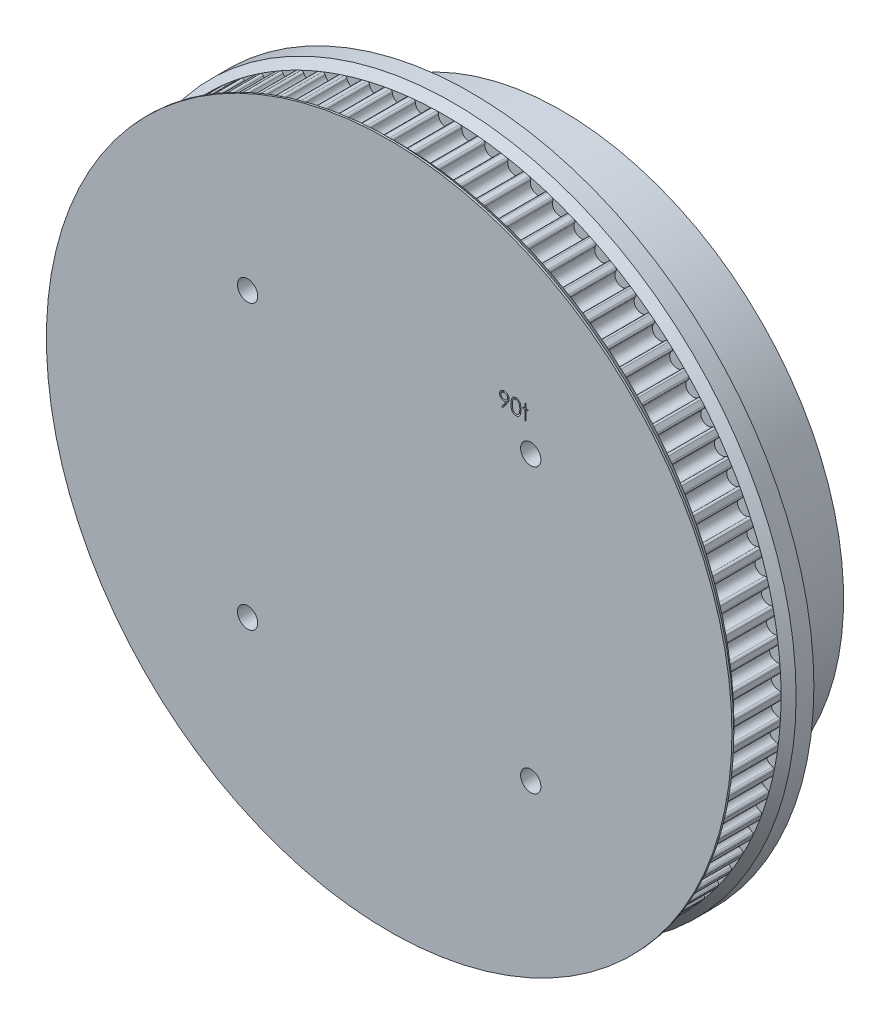
SolidWorks part; units mm, degrees
ref_plane "Front Plane" through (0, 0, 0) normal (0, 0, 1) x (1, 0, 0)
ref_plane "Top Plane" through (0, 0, 0) normal (0, 1, 0) x (1, 0, 0)
ref_plane "Right Plane" through (0, 0, 0) normal (1, 0, 0) x (0, 0, -1)
sketch "Sketch1" plane through (0, 0, 0) normal (0, 0, 1) x (1, 0, 0)
  line L0 (0, 71.6197) -> (0, 0) construction
  line L1 (0, 0) -> (4.9959, 71.4453) construction
  line L2 (0, 70.4947) -> (1.9534, 70.5727) construction
  line L3 (2.9742, 70.537) -> (4.9175, 70.323) construction
  line L4 (1.9534, 70.5727) -> (1.9653, 71.0025) construction
  line L5 (2.9742, 70.537) -> (2.9923, 70.9667) construction
  arc A0 (0, 71.6197) -> (4.9959, 71.4453) centre (0, 0) cw construction
  circle A1 centre (0, 0) radius 71.6197 construction
  circle A2 centre (0, 0) radius 71.0297
  circle A3 centre (0, 0) radius 68.9697
  circle A8 centre (0, 0) radius 72.7697 construction
  circle A9 centre (0, 70.4947) radius 1.525
  circle A10 centre (4.9175, 70.323) radius 1.525
  circle A11 centre (1.9534, 70.5727) radius 0.43
  circle A12 centre (2.9742, 70.537) radius 0.43
  point P18 (0, 68.9697)
  point P19 (4.2572, 15.8881)
  point P20 (4.2572, 15.8881)
  point P21 (1.5238, 70.5555)
  point P23 (3.4016, 70.49)
  dimension "D6" = 3.05
  dimension "D7" = 3.05
  dimension "D8" = 0.86
  dimension "D9" = 0.86
  dimension "D5" = 3.8
  dimension "D2" = 5
  dimension "D3" = 0.59
  dimension "D4" = 2.06
extrude "Boss-Extrude1" add sketch "Sketch1" along normal blind 10 contours A2
extrude "Cut-Extrude1" cut sketch "Sketch1<5>" along normal through all contours A11 A2 A9 | A12 A10 A2 | A9 | A10 region at (3.3605, 70.8449, 0) region at (1.5896, 70.9067, 0)
sketch "Sketch1<5>" plane through (0, 0, 0) normal (0, 0, 1) x (1, 0, 0) same geometry as "Sketch1"
pattern_circular "CirPattern3" count 90 over 360 about axis through (0, 0, 10) along (0, 0, 1) of "Cut-Extrude1"
sketch "Sketch2" plane through (0, 0, 10) normal (0, 0, 1) x (1, 0, 0)
  circle A0 centre (0, 0) radius 72.7697 construction
  arc A81 (-46.5195, 53.0692) -> (-44.1849, 55.0282) centre (-45.3131, 54.0021) ccw
  arc A82 (-46.5195, 53.0692) -> (-44.1849, 55.0282) centre (-45.3131, 54.0021) ccw
  arc A83 (-46.5195, 53.0692) -> (-47.1451, 53.1278) centre (-46.8597, 52.8062) ccw
  arc A84 (-46.5195, 53.0692) -> (-47.1451, 53.1278) centre (-46.8597, 52.8062) ccw
  arc A85 (-47.1451, 53.1278) -> (-47.9088, 52.4402) centre (0, 0) ccw
  arc A86 (-47.1451, 53.1278) -> (-47.9088, 52.4402) centre (0, 0) ccw
  arc A87 (-47.9088, 52.4402) -> (-47.9159, 51.8119) centre (-47.6187, 52.1227) ccw
  arc A88 (-47.9088, 52.4402) -> (-47.9159, 51.8119) centre (-47.6187, 52.1227) ccw
  arc A89 (-50.1081, 49.6949) -> (-47.9159, 51.8119) centre (-48.9698, 50.7097) ccw
  arc A90 (-50.1081, 49.6949) -> (-47.9159, 51.8119) centre (-48.9698, 50.7097) ccw
  arc A91 (-50.1081, 49.6949) -> (-50.7363, 49.7097) centre (-50.4291, 49.4088) ccw
  arc A92 (-50.1081, 49.6949) -> (-50.7363, 49.7097) centre (-50.4291, 49.4088) ccw
  arc A93 (-50.7363, 49.7097) -> (-51.4501, 48.9705) centre (0, 0) ccw
  arc A95 (-50.7363, 49.7097) -> (-51.4501, 48.9705) centre (0, 0) ccw
  arc A97 (-51.4501, 48.9705) -> (-51.4134, 48.3433) centre (-51.1386, 48.674) ccw
  arc A99 (-51.4501, 48.9705) -> (-51.4134, 48.3433) centre (-51.1386, 48.674) ccw
  arc A101 (-53.4526, 46.0785) -> (-51.4134, 48.3433) centre (-52.3878, 47.1702) ccw
  arc A103 (-53.4526, 46.0785) -> (-51.4134, 48.3433) centre (-52.3878, 47.1702) ccw
  arc A105 (-53.4526, 46.0785) -> (-54.0802, 46.0494) centre (-53.7528, 45.7707) ccw
  arc A107 (-53.4526, 46.0785) -> (-54.0802, 46.0494) centre (-53.7528, 45.7707) ccw
  arc A109 (-54.0802, 46.0494) -> (-54.7408, 45.2622) centre (0, 0) ccw
  arc A111 (-54.0802, 46.0494) -> (-54.7408, 45.2622) centre (0, 0) ccw
  arc A112 (-54.7408, 45.2622) -> (-54.6604, 44.6391) centre (-54.4094, 44.9882) ccw
  arc A114 (-54.7408, 45.2622) -> (-54.6604, 44.6391) centre (-54.4094, 44.9882) ccw
  arc A116 (-56.5367, 42.2376) -> (-54.6604, 44.6391) centre (-55.5506, 43.4009) ccw
  arc A118 (-56.5367, 42.2376) -> (-54.6604, 44.6391) centre (-55.5506, 43.4009) ccw
  arc A122 (-56.5367, 42.2376) -> (-57.1607, 42.1648) centre (-56.8147, 41.9096) ccw
  arc A126 (-56.5367, 42.2376) -> (-57.1607, 42.1648) centre (-56.8147, 41.9096) ccw
  arc A130 (-57.1607, 42.1648) -> (-57.7648, 41.3335) centre (0, 0) ccw
  arc A134 (-57.1607, 42.1648) -> (-57.7648, 41.3335) centre (0, 0) ccw
  arc A138 (-57.7648, 41.3335) -> (-57.6411, 40.7174) centre (-57.4151, 41.0832) ccw
  arc A142 (-57.7648, 41.3335) -> (-57.6411, 40.7174) centre (-57.4151, 41.0832) ccw
  arc A146 (-59.3453, 38.1909) -> (-57.6411, 40.7174) centre (-58.4428, 39.4201) ccw
  arc A150 (-59.3453, 38.1909) -> (-57.6411, 40.7174) centre (-58.4428, 39.4201) ccw
  arc A154 (-59.3453, 38.1909) -> (-59.9628, 38.0748) centre (-59.5998, 37.8443) ccw
  arc A158 (-59.3453, 38.1909) -> (-59.9628, 38.0748) centre (-59.5998, 37.8443) ccw
  arc A162 (-59.9628, 38.0748) -> (-60.5073, 37.2033) centre (0, 0) ccw
  arc A166 (-59.9628, 38.0748) -> (-60.5073, 37.2033) centre (0, 0) ccw
  arc A170 (-60.5073, 37.2033) -> (-60.341, 36.5974) centre (-60.141, 36.9781) ccw
  arc A174 (-60.5073, 37.2033) -> (-60.341, 36.5974) centre (-60.141, 36.9781) ccw
  arc A178 (-61.8648, 33.9581) -> (-60.341, 36.5974) centre (-61.0502, 35.2474) ccw
  arc A182 (-61.8648, 33.9581) -> (-60.341, 36.5974) centre (-61.0502, 35.2474) ccw
  arc A186 (-61.8648, 33.9581) -> (-62.4727, 33.7992) centre (-62.0945, 33.5946) ccw
  arc A190 (-61.8648, 33.9581) -> (-62.4727, 33.7992) centre (-62.0945, 33.5946) ccw
  arc A193 (-62.4727, 33.7992) -> (-62.9551, 32.8919) centre (0, 0) ccw
  arc A195 (-62.4727, 33.7992) -> (-62.9551, 32.8919) centre (0, 0) ccw
  arc A197 (-62.9551, 32.8919) -> (-62.7469, 32.2991) centre (-62.574, 32.6928) ccw
  arc A199 (-62.9551, 32.8919) -> (-62.7469, 32.2991) centre (-62.574, 32.6928) ccw
  arc A201 (-64.0829, 29.5599) -> (-62.7469, 32.2991) centre (-63.3602, 30.9029) ccw
  arc A203 (-64.0829, 29.5599) -> (-62.7469, 32.2991) centre (-63.3602, 30.9029) ccw
  arc A205 (-64.0829, 29.5599) -> (-64.6782, 29.359) centre (-64.2867, 29.1813) ccw
  arc A207 (-64.0829, 29.5599) -> (-64.6782, 29.359) centre (-64.2867, 29.1813) ccw
  arc A209 (-64.6782, 29.359) -> (-65.0962, 28.4202) centre (0, 0) ccw
  arc A211 (-64.6782, 29.359) -> (-65.0962, 28.4202) centre (0, 0) ccw
  arc A213 (-65.0962, 28.4202) -> (-64.8471, 27.8434) centre (-64.7021, 28.2482) ccw
  arc A215 (-65.0962, 28.4202) -> (-64.8471, 27.8434) centre (-64.7021, 28.2482) ccw
  arc A217 (-65.9888, 25.0177) -> (-64.8471, 27.8434) centre (-65.3616, 26.4078) ccw
  arc A221 (-65.9888, 25.0177) -> (-64.8471, 27.8434) centre (-65.3616, 26.4078) ccw
  arc A225 (-65.9888, 25.0177) -> (-66.5686, 24.7758) centre (-66.1656, 24.6258) ccw
  arc A229 (-65.9888, 25.0177) -> (-66.5686, 24.7758) centre (-66.1656, 24.6258) ccw
  arc A233 (-66.5686, 24.7758) -> (-66.9201, 23.8101) centre (0, 0) ccw
  arc A241 (-66.5686, 24.7758) -> (-66.9201, 23.8101) centre (0, 0) ccw
  arc A245 (-66.9201, 23.8101) -> (-66.6314, 23.2521) centre (-66.515, 23.666) ccw
  arc A247 (-66.9201, 23.8101) -> (-66.6314, 23.2521) centre (-66.515, 23.666) ccw
  arc A249 (-67.5732, 20.3537) -> (-66.6314, 23.2521) centre (-67.0445, 21.7841) ccw
  arc A251 (-67.5732, 20.3537) -> (-66.6314, 23.2521) centre (-67.0445, 21.7841) ccw
  arc A253 (-67.5732, 20.3537) -> (-68.1347, 20.0718) centre (-67.7223, 19.9503) ccw
  arc A255 (-67.5732, 20.3537) -> (-68.1347, 20.0718) centre (-67.7223, 19.9503) ccw
  arc A257 (-68.1347, 20.0718) -> (-68.418, 19.084) centre (0, 0) ccw
  arc A259 (-68.1347, 20.0718) -> (-68.418, 19.084) centre (0, 0) ccw
  arc A261 (-68.418, 19.084) -> (-68.0911, 18.5475) centre (-68.0038, 18.9685) ccw
  arc A263 (-68.418, 19.084) -> (-68.0911, 18.5475) centre (-68.0038, 18.9685) ccw
  arc A373 (3.4016, 70.49) -> (6.4418, 70.2774) centre (4.9175, 70.323) ccw
  arc A374 (3.4016, 70.49) -> (2.9923, 70.9667) centre (2.9742, 70.537) ccw
  arc A375 (2.9923, 70.9667) -> (1.9653, 71.0025) centre (0, 0) ccw
  arc A376 (1.9653, 71.0025) -> (1.5238, 70.5555) centre (1.9534, 70.5727) ccw
  arc A377 (-1.5238, 70.5555) -> (1.5238, 70.5555) centre (0, 70.4947) ccw
  arc A378 (-1.5238, 70.5555) -> (-1.9653, 71.0025) centre (-1.9534, 70.5727) ccw
  arc A379 (-1.9653, 71.0025) -> (-2.9923, 70.9667) centre (0, 0) ccw
  arc A380 (-2.9923, 70.9667) -> (-3.4016, 70.49) centre (-2.9742, 70.537) ccw
  arc A381 (-6.4418, 70.2774) -> (-3.4016, 70.49) centre (-4.9175, 70.323) ccw
  arc A382 (-6.4418, 70.2774) -> (-6.9134, 70.6925) centre (-6.8716, 70.2645) ccw
  arc A383 (-6.9134, 70.6925) -> (-7.9354, 70.5851) centre (0, 0) ccw
  arc A384 (-7.9354, 70.5851) -> (-8.3105, 70.081) centre (-7.8874, 70.1578) ccw
  arc A385 (-11.3284, 69.6568) -> (-8.3105, 70.081) centre (-9.811, 69.8087) ccw
  arc A386 (-11.3284, 69.6568) -> (-11.8279, 70.038) centre (-11.7563, 69.614) ccw
  arc A387 (-11.8279, 70.038) -> (-12.8399, 69.8596) centre (0, 0) ccw
  arc A388 (-12.8399, 69.8596) -> (-13.1788, 69.3305) centre (-12.7621, 69.4367) ccw
  arc A389 (-16.1598, 68.6969) -> (-13.1788, 69.3305) centre (-14.6567, 68.9542) ccw
  arc A390 (-16.1598, 68.6969) -> (-16.6847, 69.0423) centre (-16.5836, 68.6244) ccw
  arc A391 (-16.6847, 69.0423) -> (-17.6817, 68.7937) centre (0, 0) ccw
  arc A392 (-17.6817, 68.7937) -> (-17.983, 68.2424) centre (-17.5747, 68.3773) ccw
  arc A393 (-20.9125, 67.4023) -> (-17.983, 68.2424) centre (-19.431, 67.7639) ccw
  arc A394 (-20.9125, 67.4023) -> (-21.4602, 67.7103) centre (-21.3302, 67.3004) ccw
  arc A395 (-21.4602, 67.7103) -> (-22.4375, 67.3927) centre (0, 0) ccw
  arc A396 (-22.4375, 67.3927) -> (-22.6995, 66.8217) centre (-22.3016, 66.9848) ccw
  arc A397 (-25.5633, 65.7794) -> (-22.6995, 66.8217) centre (-24.1106, 66.2434) ccw
  arc A398 (-25.5633, 65.7794) -> (-26.1311, 66.0484) centre (-25.9729, 65.6485) ccw
  arc A399 (-26.1311, 66.0484) -> (-27.0839, 65.6634) centre (0, 0) ccw
  arc A400 (-27.0839, 65.6634) -> (-27.3055, 65.0755) centre (-26.9199, 65.2659) ccw
  arc A401 (-30.0896, 63.8359) -> (-27.3055, 65.0755) centre (-28.6728, 64.4001) ccw
  arc A402 (-30.0896, 63.8359) -> (-30.6748, 64.0647) centre (-30.4891, 63.6768) ccw
  arc A403 (-30.6748, 64.0647) -> (-31.5984, 63.6142) centre (0, 0) ccw
  arc A404 (-31.5984, 63.6142) -> (-31.7784, 63.0122) centre (-31.4071, 63.2291) ccw
  arc A405 (-34.4692, 61.5815) -> (-31.7784, 63.0122) centre (-33.0953, 62.2431) ccw
  arc A406 (-34.4692, 61.5815) -> (-35.069, 61.7688) centre (-34.8567, 61.3949) ccw
  arc A407 (-35.069, 61.7688) -> (-35.9589, 61.255) centre (0, 0) ccw
  arc A408 (-35.9589, 61.255) -> (-36.0965, 60.642) centre (-35.7412, 60.8842) ccw
  arc A409 (-38.681, 59.027) -> (-36.0965, 60.642) centre (-37.3565, 59.7829) ccw
  arc A410 (-38.681, 59.027) -> (-39.2923, 59.1721) centre (-39.0544, 58.8139) ccw
  arc A411 (-39.2923, 59.1721) -> (-40.1442, 58.5975) centre (0, 0) ccw
  arc A412 (-40.1442, 58.5975) -> (-40.2387, 57.9763) centre (-39.9012, 58.2427) ccw
  arc A413 (-42.7043, 56.185) -> (-40.2387, 57.9763) centre (-41.4358, 57.0314) ccw
  arc A414 (-42.7043, 56.185) -> (-43.3242, 56.2871) centre (-43.062, 55.9463) ccw
  arc A415 (-43.3242, 56.2871) -> (-44.134, 55.6544) centre (0, 0) ccw
  arc A416 (-44.134, 55.6544) -> (-44.1849, 55.0282) centre (-43.8668, 55.3175) ccw
  arc A649 (3.4016, 70.49) -> (6.4418, 70.2774) centre (4.9175, 70.323) ccw
  arc A650 (3.4016, 70.49) -> (2.9923, 70.9667) centre (2.9742, 70.537) ccw
  arc A651 (2.9923, 70.9667) -> (1.9653, 71.0025) centre (0, 0) ccw
  arc A652 (1.9653, 71.0025) -> (1.5238, 70.5555) centre (1.9534, 70.5727) ccw
  arc A653 (-1.5238, 70.5555) -> (1.5238, 70.5555) centre (0, 70.4947) ccw
  arc A654 (-1.5238, 70.5555) -> (-1.9653, 71.0025) centre (-1.9534, 70.5727) ccw
  arc A655 (-1.9653, 71.0025) -> (-2.9923, 70.9667) centre (0, 0) ccw
  arc A656 (-2.9923, 70.9667) -> (-3.4016, 70.49) centre (-2.9742, 70.537) ccw
  arc A657 (-6.4418, 70.2774) -> (-3.4016, 70.49) centre (-4.9175, 70.323) ccw
  arc A658 (-6.4418, 70.2774) -> (-6.9134, 70.6925) centre (-6.8716, 70.2645) ccw
  arc A659 (-6.9134, 70.6925) -> (-7.9354, 70.5851) centre (0, 0) ccw
  arc A660 (-7.9354, 70.5851) -> (-8.3105, 70.081) centre (-7.8874, 70.1578) ccw
  arc A661 (-11.3284, 69.6568) -> (-8.3105, 70.081) centre (-9.811, 69.8087) ccw
  arc A662 (-11.3284, 69.6568) -> (-11.8279, 70.038) centre (-11.7563, 69.614) ccw
  arc A663 (-11.8279, 70.038) -> (-12.8399, 69.8596) centre (0, 0) ccw
  arc A664 (-12.8399, 69.8596) -> (-13.1788, 69.3305) centre (-12.7621, 69.4367) ccw
  arc A665 (-16.1598, 68.6969) -> (-13.1788, 69.3305) centre (-14.6567, 68.9542) ccw
  arc A666 (-16.1598, 68.6969) -> (-16.6847, 69.0423) centre (-16.5836, 68.6244) ccw
  arc A667 (-16.6847, 69.0423) -> (-17.6817, 68.7937) centre (0, 0) ccw
  arc A668 (-17.6817, 68.7937) -> (-17.983, 68.2424) centre (-17.5747, 68.3773) ccw
  arc A669 (-20.9125, 67.4023) -> (-17.983, 68.2424) centre (-19.431, 67.7639) ccw
  arc A670 (-20.9125, 67.4023) -> (-21.4602, 67.7103) centre (-21.3302, 67.3004) ccw
  arc A671 (-21.4602, 67.7103) -> (-22.4375, 67.3927) centre (0, 0) ccw
  arc A672 (-22.4375, 67.3927) -> (-22.6995, 66.8217) centre (-22.3016, 66.9848) ccw
  arc A673 (-25.5633, 65.7794) -> (-22.6995, 66.8217) centre (-24.1106, 66.2434) ccw
  arc A674 (-25.5633, 65.7794) -> (-26.1311, 66.0484) centre (-25.9729, 65.6485) ccw
  arc A675 (-26.1311, 66.0484) -> (-27.0839, 65.6634) centre (0, 0) ccw
  arc A676 (-27.0839, 65.6634) -> (-27.3055, 65.0755) centre (-26.9199, 65.2659) ccw
  arc A677 (-30.0896, 63.8359) -> (-27.3055, 65.0755) centre (-28.6728, 64.4001) ccw
  arc A678 (-30.0896, 63.8359) -> (-30.6748, 64.0647) centre (-30.4891, 63.6768) ccw
  arc A679 (-30.6748, 64.0647) -> (-31.5984, 63.6142) centre (0, 0) ccw
  arc A680 (-31.5984, 63.6142) -> (-31.7784, 63.0122) centre (-31.4071, 63.2291) ccw
  arc A681 (-34.4692, 61.5815) -> (-31.7784, 63.0122) centre (-33.0953, 62.2431) ccw
  arc A682 (-34.4692, 61.5815) -> (-35.069, 61.7688) centre (-34.8567, 61.3949) ccw
  arc A683 (-35.069, 61.7688) -> (-35.9589, 61.255) centre (0, 0) ccw
  arc A684 (-35.9589, 61.255) -> (-36.0965, 60.642) centre (-35.7412, 60.8842) ccw
  arc A685 (-38.681, 59.027) -> (-36.0965, 60.642) centre (-37.3565, 59.7829) ccw
  arc A686 (-38.681, 59.027) -> (-39.2923, 59.1721) centre (-39.0544, 58.8139) ccw
  arc A687 (-39.2923, 59.1721) -> (-40.1442, 58.5975) centre (0, 0) ccw
  arc A688 (-40.1442, 58.5975) -> (-40.2387, 57.9763) centre (-39.9012, 58.2427) ccw
  arc A689 (-42.7043, 56.185) -> (-40.2387, 57.9763) centre (-41.4358, 57.0314) ccw
  arc A690 (-42.7043, 56.185) -> (-43.3242, 56.2871) centre (-43.062, 55.9463) ccw
  arc A691 (-43.3242, 56.2871) -> (-44.134, 55.6544) centre (0, 0) ccw
  arc A692 (-44.134, 55.6544) -> (-44.1849, 55.0282) centre (-43.8668, 55.3175) ccw
  arc A1359 (-6.9134, -70.6925) -> (-6.4418, -70.2774) centre (-6.8716, -70.2645) ccw
  arc A1361 (-6.9134, -70.6925) -> (-6.4418, -70.2774) centre (-6.8716, -70.2645) ccw
  arc A1363 (-3.4016, -70.49) -> (-6.4418, -70.2774) centre (-4.9175, -70.323) ccw
  arc A1365 (-3.4016, -70.49) -> (-6.4418, -70.2774) centre (-4.9175, -70.323) ccw
  arc A1367 (-3.4016, -70.49) -> (-2.9923, -70.9667) centre (-2.9742, -70.537) ccw
  arc A1369 (-3.4016, -70.49) -> (-2.9923, -70.9667) centre (-2.9742, -70.537) ccw
  arc A1371 (-2.9923, -70.9667) -> (-1.9653, -71.0025) centre (0, 0) ccw
  arc A1373 (-2.9923, -70.9667) -> (-1.9653, -71.0025) centre (0, 0) ccw
  arc A1375 (-1.9653, -71.0025) -> (-1.5238, -70.5555) centre (-1.9534, -70.5727) ccw
  arc A1377 (-1.9653, -71.0025) -> (-1.5238, -70.5555) centre (-1.9534, -70.5727) ccw
  arc A1379 (1.5238, -70.5555) -> (-1.5238, -70.5555) centre (0, -70.4947) ccw
  arc A1381 (1.5238, -70.5555) -> (-1.5238, -70.5555) centre (0, -70.4947) ccw
  arc A1383 (1.5238, -70.5555) -> (1.9653, -71.0025) centre (1.9534, -70.5727) ccw
  arc A1385 (1.5238, -70.5555) -> (1.9653, -71.0025) centre (1.9534, -70.5727) ccw
  arc A1387 (1.9653, -71.0025) -> (2.9923, -70.9667) centre (0, 0) ccw
  arc A1389 (1.9653, -71.0025) -> (2.9923, -70.9667) centre (0, 0) ccw
  arc A1391 (2.9923, -70.9667) -> (3.4016, -70.49) centre (2.9742, -70.537) ccw
  arc A1393 (2.9923, -70.9667) -> (3.4016, -70.49) centre (2.9742, -70.537) ccw
  arc A1395 (6.4418, -70.2774) -> (3.4016, -70.49) centre (4.9175, -70.323) ccw
  arc A1397 (6.4418, -70.2774) -> (3.4016, -70.49) centre (4.9175, -70.323) ccw
  arc A1399 (6.4418, -70.2774) -> (6.9134, -70.6925) centre (6.8716, -70.2645) ccw
  arc A1401 (6.4418, -70.2774) -> (6.9134, -70.6925) centre (6.8716, -70.2645) ccw
  arc A1403 (6.9134, -70.6925) -> (7.9354, -70.5851) centre (0, 0) ccw
  arc A1405 (6.9134, -70.6925) -> (7.9354, -70.5851) centre (0, 0) ccw
  arc A1407 (7.9354, -70.5851) -> (8.3105, -70.081) centre (7.8874, -70.1578) ccw
  arc A1409 (7.9354, -70.5851) -> (8.3105, -70.081) centre (7.8874, -70.1578) ccw
  arc A1411 (11.3284, -69.6568) -> (8.3105, -70.081) centre (9.811, -69.8087) ccw
  arc A1413 (11.3284, -69.6568) -> (8.3105, -70.081) centre (9.811, -69.8087) ccw
  arc A1415 (11.3284, -69.6568) -> (11.8279, -70.038) centre (11.7563, -69.614) ccw
  arc A1417 (11.3284, -69.6568) -> (11.8279, -70.038) centre (11.7563, -69.614) ccw
  arc A1419 (11.8279, -70.038) -> (12.8399, -69.8596) centre (0, 0) ccw
  arc A1421 (11.8279, -70.038) -> (12.8399, -69.8596) centre (0, 0) ccw
  arc A1423 (12.8399, -69.8596) -> (13.1788, -69.3305) centre (12.7621, -69.4367) ccw
  arc A1425 (12.8399, -69.8596) -> (13.1788, -69.3305) centre (12.7621, -69.4367) ccw
  arc A1427 (16.1598, -68.6969) -> (13.1788, -69.3305) centre (14.6567, -68.9542) ccw
  arc A1429 (16.1598, -68.6969) -> (13.1788, -69.3305) centre (14.6567, -68.9542) ccw
  arc A1431 (16.1598, -68.6969) -> (16.6847, -69.0423) centre (16.5836, -68.6244) ccw
  arc A1433 (16.1598, -68.6969) -> (16.6847, -69.0423) centre (16.5836, -68.6244) ccw
  arc A1435 (16.6847, -69.0423) -> (17.6817, -68.7937) centre (0, 0) ccw
  arc A1437 (16.6847, -69.0423) -> (17.6817, -68.7937) centre (0, 0) ccw
  arc A1439 (17.6817, -68.7937) -> (17.983, -68.2424) centre (17.5747, -68.3773) ccw
  arc A1441 (17.6817, -68.7937) -> (17.983, -68.2424) centre (17.5747, -68.3773) ccw
  arc A1443 (20.9125, -67.4023) -> (17.983, -68.2424) centre (19.431, -67.7639) ccw
  arc A1445 (20.9125, -67.4023) -> (17.983, -68.2424) centre (19.431, -67.7639) ccw
  arc A1447 (20.9125, -67.4023) -> (21.4602, -67.7103) centre (21.3302, -67.3004) ccw
  arc A1449 (20.9125, -67.4023) -> (21.4602, -67.7103) centre (21.3302, -67.3004) ccw
  arc A1451 (21.4602, -67.7103) -> (22.4375, -67.3927) centre (0, 0) ccw
  arc A1453 (21.4602, -67.7103) -> (22.4375, -67.3927) centre (0, 0) ccw
  arc A1455 (22.4375, -67.3927) -> (22.6995, -66.8217) centre (22.3016, -66.9848) ccw
  arc A1457 (22.4375, -67.3927) -> (22.6995, -66.8217) centre (22.3016, -66.9848) ccw
  arc A1459 (25.5633, -65.7794) -> (22.6995, -66.8217) centre (24.1106, -66.2434) ccw
  arc A1461 (25.5633, -65.7794) -> (22.6995, -66.8217) centre (24.1106, -66.2434) ccw
  arc A1463 (25.5633, -65.7794) -> (26.1311, -66.0484) centre (25.9729, -65.6485) ccw
  arc A1465 (25.5633, -65.7794) -> (26.1311, -66.0484) centre (25.9729, -65.6485) ccw
  arc A1467 (26.1311, -66.0484) -> (27.0839, -65.6634) centre (0, 0) ccw
  arc A1469 (26.1311, -66.0484) -> (27.0839, -65.6634) centre (0, 0) ccw
  arc A1471 (27.0839, -65.6634) -> (27.3055, -65.0755) centre (26.9199, -65.2659) ccw
  arc A1473 (27.0839, -65.6634) -> (27.3055, -65.0755) centre (26.9199, -65.2659) ccw
  arc A1475 (30.0896, -63.8359) -> (27.3055, -65.0755) centre (28.6728, -64.4001) ccw
  arc A1477 (30.0896, -63.8359) -> (27.3055, -65.0755) centre (28.6728, -64.4001) ccw
  arc A1479 (30.0896, -63.8359) -> (30.6748, -64.0647) centre (30.4891, -63.6768) ccw
  arc A1481 (30.0896, -63.8359) -> (30.6748, -64.0647) centre (30.4891, -63.6768) ccw
  arc A1483 (30.6748, -64.0647) -> (31.5984, -63.6142) centre (0, 0) ccw
  arc A1485 (30.6748, -64.0647) -> (31.5984, -63.6142) centre (0, 0) ccw
  arc A1487 (31.5984, -63.6142) -> (31.7784, -63.0122) centre (31.4071, -63.2291) ccw
  arc A1489 (31.5984, -63.6142) -> (31.7784, -63.0122) centre (31.4071, -63.2291) ccw
  arc A1491 (34.4692, -61.5815) -> (31.7784, -63.0122) centre (33.0953, -62.2431) ccw
  arc A1493 (34.4692, -61.5815) -> (31.7784, -63.0122) centre (33.0953, -62.2431) ccw
  arc A1495 (34.4692, -61.5815) -> (35.069, -61.7688) centre (34.8567, -61.3949) ccw
  arc A1497 (34.4692, -61.5815) -> (35.069, -61.7688) centre (34.8567, -61.3949) ccw
  arc A1499 (35.069, -61.7688) -> (35.9589, -61.255) centre (0, 0) ccw
  arc A1501 (35.069, -61.7688) -> (35.9589, -61.255) centre (0, 0) ccw
  arc A1503 (35.9589, -61.255) -> (36.0965, -60.642) centre (35.7412, -60.8842) ccw
  arc A1505 (35.9589, -61.255) -> (36.0965, -60.642) centre (35.7412, -60.8842) ccw
  arc A1507 (38.681, -59.027) -> (36.0965, -60.642) centre (37.3565, -59.7829) ccw
  arc A1509 (38.681, -59.027) -> (36.0965, -60.642) centre (37.3565, -59.7829) ccw
  arc A1511 (38.681, -59.027) -> (39.2923, -59.1721) centre (39.0544, -58.8139) ccw
  arc A1513 (38.681, -59.027) -> (39.2923, -59.1721) centre (39.0544, -58.8139) ccw
  arc A1515 (39.2923, -59.1721) -> (40.1442, -58.5975) centre (0, 0) ccw
  arc A1517 (39.2923, -59.1721) -> (40.1442, -58.5975) centre (0, 0) ccw
  arc A1519 (40.1442, -58.5975) -> (40.2387, -57.9763) centre (39.9012, -58.2427) ccw
  arc A1521 (40.1442, -58.5975) -> (40.2387, -57.9763) centre (39.9012, -58.2427) ccw
  arc A1523 (42.7043, -56.185) -> (40.2387, -57.9763) centre (41.4358, -57.0314) ccw
  arc A1525 (42.7043, -56.185) -> (40.2387, -57.9763) centre (41.4358, -57.0314) ccw
  arc A1527 (42.7043, -56.185) -> (43.3242, -56.2871) centre (43.062, -55.9463) ccw
  arc A1529 (42.7043, -56.185) -> (43.3242, -56.2871) centre (43.062, -55.9463) ccw
  arc A1531 (43.3242, -56.2871) -> (44.134, -55.6544) centre (0, 0) ccw
  arc A1533 (43.3242, -56.2871) -> (44.134, -55.6544) centre (0, 0) ccw
  arc A1535 (44.134, -55.6544) -> (44.1849, -55.0282) centre (43.8668, -55.3175) ccw
  arc A1537 (44.134, -55.6544) -> (44.1849, -55.0282) centre (43.8668, -55.3175) ccw
  arc A1539 (46.5195, -53.0692) -> (44.1849, -55.0282) centre (45.3131, -54.0021) ccw
  arc A1541 (46.5195, -53.0692) -> (44.1849, -55.0282) centre (45.3131, -54.0021) ccw
  arc A1543 (46.5195, -53.0692) -> (47.1451, -53.1278) centre (46.8597, -52.8062) ccw
  arc A1545 (46.5195, -53.0692) -> (47.1451, -53.1278) centre (46.8597, -52.8062) ccw
  arc A1547 (47.1451, -53.1278) -> (47.9088, -52.4402) centre (0, 0) ccw
  arc A1549 (47.1451, -53.1278) -> (47.9088, -52.4402) centre (0, 0) ccw
  arc A1551 (47.9088, -52.4402) -> (47.9159, -51.8119) centre (47.6187, -52.1227) ccw
  arc A1553 (47.9088, -52.4402) -> (47.9159, -51.8119) centre (47.6187, -52.1227) ccw
  arc A1555 (50.1081, -49.6949) -> (47.9159, -51.8119) centre (48.9698, -50.7097) ccw
  arc A1557 (50.1081, -49.6949) -> (47.9159, -51.8119) centre (48.9698, -50.7097) ccw
  arc A1559 (50.1081, -49.6949) -> (50.7363, -49.7097) centre (50.4291, -49.4088) ccw
  arc A1561 (50.1081, -49.6949) -> (50.7363, -49.7097) centre (50.4291, -49.4088) ccw
  arc A1563 (50.7363, -49.7097) -> (51.4501, -48.9705) centre (0, 0) ccw
  arc A1565 (50.7363, -49.7097) -> (51.4501, -48.9705) centre (0, 0) ccw
  arc A1567 (51.4501, -48.9705) -> (51.4134, -48.3433) centre (51.1386, -48.674) ccw
  arc A1569 (51.4501, -48.9705) -> (51.4134, -48.3433) centre (51.1386, -48.674) ccw
  arc A1571 (53.4526, -46.0785) -> (51.4134, -48.3433) centre (52.3878, -47.1702) ccw
  arc A1573 (53.4526, -46.0785) -> (51.4134, -48.3433) centre (52.3878, -47.1702) ccw
  arc A1575 (53.4526, -46.0785) -> (54.0802, -46.0494) centre (53.7528, -45.7707) ccw
  arc A1577 (53.4526, -46.0785) -> (54.0802, -46.0494) centre (53.7528, -45.7707) ccw
  arc A1579 (54.0802, -46.0494) -> (54.7408, -45.2622) centre (0, 0) ccw
  arc A1581 (54.0802, -46.0494) -> (54.7408, -45.2622) centre (0, 0) ccw
  arc A1583 (54.7408, -45.2622) -> (54.6604, -44.6391) centre (54.4094, -44.9882) ccw
  arc A1585 (54.7408, -45.2622) -> (54.6604, -44.6391) centre (54.4094, -44.9882) ccw
  arc A1587 (56.5367, -42.2376) -> (54.6604, -44.6391) centre (55.5506, -43.4009) ccw
  arc A1589 (56.5367, -42.2376) -> (54.6604, -44.6391) centre (55.5506, -43.4009) ccw
  arc A1591 (56.5367, -42.2376) -> (57.1607, -42.1648) centre (56.8147, -41.9096) ccw
  arc A1593 (56.5367, -42.2376) -> (57.1607, -42.1648) centre (56.8147, -41.9096) ccw
  arc A1595 (57.1607, -42.1648) -> (57.7648, -41.3335) centre (0, 0) ccw
  arc A1596 (57.1607, -42.1648) -> (57.7648, -41.3335) centre (0, 0) ccw
  arc A1597 (57.7648, -41.3335) -> (57.6411, -40.7174) centre (57.4151, -41.0832) ccw
  arc A1598 (57.7648, -41.3335) -> (57.6411, -40.7174) centre (57.4151, -41.0832) ccw
  arc A1599 (59.3453, -38.1909) -> (57.6411, -40.7174) centre (58.4428, -39.4201) ccw
  arc A1600 (59.3453, -38.1909) -> (57.6411, -40.7174) centre (58.4428, -39.4201) ccw
  arc A1601 (59.3453, -38.1909) -> (59.9628, -38.0748) centre (59.5998, -37.8443) ccw
  arc A1602 (59.3453, -38.1909) -> (59.9628, -38.0748) centre (59.5998, -37.8443) ccw
  arc A1603 (59.9628, -38.0748) -> (60.5073, -37.2033) centre (0, 0) ccw
  arc A1604 (59.9628, -38.0748) -> (60.5073, -37.2033) centre (0, 0) ccw
  arc A1605 (60.5073, -37.2033) -> (60.341, -36.5974) centre (60.141, -36.9781) ccw
  arc A1606 (60.5073, -37.2033) -> (60.341, -36.5974) centre (60.141, -36.9781) ccw
  arc A1607 (61.8648, -33.9581) -> (60.341, -36.5974) centre (61.0502, -35.2474) ccw
  arc A1608 (61.8648, -33.9581) -> (60.341, -36.5974) centre (61.0502, -35.2474) ccw
  arc A1609 (61.8648, -33.9581) -> (62.4727, -33.7992) centre (62.0945, -33.5946) ccw
  arc A1610 (61.8648, -33.9581) -> (62.4727, -33.7992) centre (62.0945, -33.5946) ccw
  arc A1611 (62.4727, -33.7992) -> (62.9551, -32.8919) centre (0, 0) ccw
  arc A1612 (62.4727, -33.7992) -> (62.9551, -32.8919) centre (0, 0) ccw
  arc A1613 (62.9551, -32.8919) -> (62.7469, -32.2991) centre (62.574, -32.6928) ccw
  arc A1614 (62.9551, -32.8919) -> (62.7469, -32.2991) centre (62.574, -32.6928) ccw
  arc A1615 (64.0829, -29.5599) -> (62.7469, -32.2991) centre (63.3602, -30.9029) ccw
  arc A1616 (64.0829, -29.5599) -> (62.7469, -32.2991) centre (63.3602, -30.9029) ccw
  arc A1617 (64.0829, -29.5599) -> (64.6782, -29.359) centre (64.2867, -29.1813) ccw
  arc A1618 (64.0829, -29.5599) -> (64.6782, -29.359) centre (64.2867, -29.1813) ccw
  arc A1619 (64.6782, -29.359) -> (65.0962, -28.4202) centre (0, 0) ccw
  arc A1620 (64.6782, -29.359) -> (65.0962, -28.4202) centre (0, 0) ccw
  arc A1621 (65.0962, -28.4202) -> (64.8471, -27.8434) centre (64.7021, -28.2482) ccw
  arc A1622 (65.0962, -28.4202) -> (64.8471, -27.8434) centre (64.7021, -28.2482) ccw
  arc A1623 (65.9888, -25.0177) -> (64.8471, -27.8434) centre (65.3616, -26.4078) ccw
  arc A1624 (65.9888, -25.0177) -> (64.8471, -27.8434) centre (65.3616, -26.4078) ccw
  arc A1625 (65.9888, -25.0177) -> (66.5686, -24.7758) centre (66.1656, -24.6258) ccw
  arc A1626 (65.9888, -25.0177) -> (66.5686, -24.7758) centre (66.1656, -24.6258) ccw
  arc A1627 (66.5686, -24.7758) -> (66.9201, -23.8101) centre (0, 0) ccw
  arc A1628 (66.5686, -24.7758) -> (66.9201, -23.8101) centre (0, 0) ccw
  arc A1629 (66.9201, -23.8101) -> (66.6314, -23.2521) centre (66.515, -23.666) ccw
  arc A1630 (66.9201, -23.8101) -> (66.6314, -23.2521) centre (66.515, -23.666) ccw
  arc A1631 (67.5732, -20.3537) -> (66.6314, -23.2521) centre (67.0445, -21.7841) ccw
  arc A1632 (67.5732, -20.3537) -> (66.6314, -23.2521) centre (67.0445, -21.7841) ccw
  arc A1633 (67.5732, -20.3537) -> (68.1347, -20.0718) centre (67.7223, -19.9503) ccw
  arc A1634 (67.5732, -20.3537) -> (68.1347, -20.0718) centre (67.7223, -19.9503) ccw
  arc A1635 (68.1347, -20.0718) -> (68.418, -19.084) centre (0, 0) ccw
  arc A1636 (68.1347, -20.0718) -> (68.418, -19.084) centre (0, 0) ccw
  arc A1637 (68.418, -19.084) -> (68.0911, -18.5475) centre (68.0038, -18.9685) ccw
  arc A1638 (68.418, -19.084) -> (68.0911, -18.5475) centre (68.0038, -18.9685) ccw
  arc A1639 (68.8284, -15.5904) -> (68.0911, -18.5475) centre (68.4007, -17.0542) ccw
  arc A1640 (68.8284, -15.5904) -> (68.0911, -18.5475) centre (68.4007, -17.0542) ccw
  arc A1641 (68.8284, -15.5904) -> (69.3689, -15.2701) centre (68.949, -15.1777) ccw
  arc A1642 (68.8284, -15.5904) -> (69.3689, -15.2701) centre (68.949, -15.1777) ccw
  arc A1643 (69.3689, -15.2701) -> (69.5826, -14.2649) centre (0, 0) ccw
  arc A1644 (69.3689, -15.2701) -> (69.5826, -14.2649) centre (0, 0) ccw
  arc A1645 (69.5826, -14.2649) -> (69.219, -13.7525) centre (69.1613, -14.1786) ccw
  arc A1646 (69.5826, -14.2649) -> (69.219, -13.7525) centre (69.1613, -14.1786) ccw
  arc A1647 (69.7483, -10.7512) -> (69.219, -13.7525) centre (69.4238, -12.2413) ccw
  arc A1648 (69.7483, -10.7512) -> (69.219, -13.7525) centre (69.4238, -12.2413) ccw
  arc A1649 (69.7483, -10.7512) -> (70.2651, -10.394) centre (69.8397, -10.3311) ccw
  arc A1650 (69.7483, -10.7512) -> (70.2651, -10.394) centre (69.8397, -10.3311) ccw
  arc A1651 (70.2651, -10.394) -> (70.4081, -9.3764) centre (0, 0) ccw
  arc A1652 (70.2651, -10.394) -> (70.4081, -9.3764) centre (0, 0) ccw
  arc A1653 (70.4081, -9.3764) -> (70.0098, -8.8905) centre (69.9819, -9.3196) ccw
  arc A1654 (70.4081, -9.3764) -> (70.0098, -8.8905) centre (69.9819, -9.3196) ccw
  arc A1655 (70.3283, -5.8596) -> (70.0098, -8.8905) centre (70.1085, -7.3687) ccw
  arc A1656 (70.3283, -5.8596) -> (70.0098, -8.8905) centre (70.1085, -7.3687) ccw
  arc A1657 (70.3283, -5.8596) -> (70.819, -5.4672) centre (70.3903, -5.4341) ccw
  arc A1658 (70.3283, -5.8596) -> (70.819, -5.4672) centre (70.3903, -5.4341) ccw
  arc A1659 (70.819, -5.4672) -> (70.8907, -4.4421) centre (0, 0) ccw
  arc A1660 (70.819, -5.4672) -> (70.8907, -4.4421) centre (0, 0) ccw
  arc A1661 (70.8907, -4.4421) -> (70.4594, -3.9852) centre (70.4615, -4.4152) ccw
  arc A1662 (70.8907, -4.4421) -> (70.4594, -3.9852) centre (70.4615, -4.4152) ccw
  arc A1663 (70.5657, -0.9395) -> (70.4594, -3.9852) centre (70.4518, -2.4602) ccw
  arc A1664 (70.5657, -0.9395) -> (70.4594, -3.9852) centre (70.4518, -2.4602) ccw
  arc A1665 (70.5657, -0.9395) -> (71.0279, -0.5138) centre (70.5979, -0.5107) ccw
  arc A1666 (70.5657, -0.9395) -> (71.0279, -0.5138) centre (70.5979, -0.5107) ccw
  arc A1667 (71.0279, -0.5138) -> (71.0279, 0.5138) centre (0, 0) ccw
  arc A1668 (71.0279, -0.5138) -> (71.0279, 0.5138) centre (0, 0) ccw
  arc A1669 (71.0279, 0.5138) -> (70.5657, 0.9395) centre (70.5979, 0.5107) ccw
  arc A1670 (71.0279, 0.5138) -> (70.5657, 0.9395) centre (70.5979, 0.5107) ccw
  arc A1671 (-68.8284, 15.5904) -> (-68.0911, 18.5475) centre (-68.4007, 17.0542) ccw
  arc A1672 (-68.8284, 15.5904) -> (-68.0911, 18.5475) centre (-68.4007, 17.0542) ccw
  arc A1673 (-68.8284, 15.5904) -> (-69.3689, 15.2701) centre (-68.949, 15.1777) ccw
  arc A1674 (-68.8284, 15.5904) -> (-69.3689, 15.2701) centre (-68.949, 15.1777) ccw
  arc A1675 (-69.3689, 15.2701) -> (-69.5826, 14.2649) centre (0, 0) ccw
  arc A1676 (-69.3689, 15.2701) -> (-69.5826, 14.2649) centre (0, 0) ccw
  arc A1677 (-69.5826, 14.2649) -> (-69.219, 13.7525) centre (-69.1613, 14.1786) ccw
  arc A1678 (-69.5826, 14.2649) -> (-69.219, 13.7525) centre (-69.1613, 14.1786) ccw
  arc A1679 (-69.7483, 10.7512) -> (-69.219, 13.7525) centre (-69.4238, 12.2413) ccw
  arc A1680 (-69.7483, 10.7512) -> (-69.219, 13.7525) centre (-69.4238, 12.2413) ccw
  arc A1681 (-69.7483, 10.7512) -> (-70.2651, 10.394) centre (-69.8397, 10.3311) ccw
  arc A1682 (-69.7483, 10.7512) -> (-70.2651, 10.394) centre (-69.8397, 10.3311) ccw
  arc A1683 (-70.2651, 10.394) -> (-70.4081, 9.3764) centre (0, 0) ccw
  arc A1684 (-70.2651, 10.394) -> (-70.4081, 9.3764) centre (0, 0) ccw
  arc A1685 (-70.4081, 9.3764) -> (-70.0098, 8.8905) centre (-69.9819, 9.3196) ccw
  arc A1686 (-70.4081, 9.3764) -> (-70.0098, 8.8905) centre (-69.9819, 9.3196) ccw
  arc A1687 (-70.3283, 5.8596) -> (-70.0098, 8.8905) centre (-70.1085, 7.3687) ccw
  arc A1688 (-70.3283, 5.8596) -> (-70.0098, 8.8905) centre (-70.1085, 7.3687) ccw
  arc A1689 (-70.3283, 5.8596) -> (-70.819, 5.4672) centre (-70.3903, 5.4341) ccw
  arc A1690 (-70.3283, 5.8596) -> (-70.819, 5.4672) centre (-70.3903, 5.4341) ccw
  arc A1691 (-70.819, 5.4672) -> (-70.8907, 4.4421) centre (0, 0) ccw
  arc A1692 (-70.819, 5.4672) -> (-70.8907, 4.4421) centre (0, 0) ccw
  arc A1693 (-70.8907, 4.4421) -> (-70.4594, 3.9852) centre (-70.4615, 4.4152) ccw
  arc A1694 (-70.8907, 4.4421) -> (-70.4594, 3.9852) centre (-70.4615, 4.4152) ccw
  arc A1695 (-70.5657, 0.9395) -> (-70.4594, 3.9852) centre (-70.4518, 2.4602) ccw
  arc A1696 (-70.5657, 0.9395) -> (-70.4594, 3.9852) centre (-70.4518, 2.4602) ccw
  arc A1697 (-70.5657, 0.9395) -> (-71.0279, 0.5138) centre (-70.5979, 0.5107) ccw
  arc A1698 (-70.5657, 0.9395) -> (-71.0279, 0.5138) centre (-70.5979, 0.5107) ccw
  arc A1699 (-71.0279, 0.5138) -> (-71.0279, -0.5138) centre (0, 0) ccw
  arc A1700 (-71.0279, 0.5138) -> (-71.0279, -0.5138) centre (0, 0) ccw
  arc A1701 (-71.0279, -0.5138) -> (-70.5657, -0.9395) centre (-70.5979, -0.5107) ccw
  arc A1702 (-71.0279, -0.5138) -> (-70.5657, -0.9395) centre (-70.5979, -0.5107) ccw
  arc A1703 (-70.4594, -3.9852) -> (-70.5657, -0.9395) centre (-70.4518, -2.4602) ccw
  arc A1704 (-70.4594, -3.9852) -> (-70.5657, -0.9395) centre (-70.4518, -2.4602) ccw
  arc A1705 (-70.4594, -3.9852) -> (-70.8907, -4.4421) centre (-70.4615, -4.4152) ccw
  arc A1706 (-70.4594, -3.9852) -> (-70.8907, -4.4421) centre (-70.4615, -4.4152) ccw
  arc A1707 (-70.8907, -4.4421) -> (-70.819, -5.4672) centre (0, 0) ccw
  arc A1708 (-70.8907, -4.4421) -> (-70.819, -5.4672) centre (0, 0) ccw
  arc A1709 (-70.819, -5.4672) -> (-70.3283, -5.8596) centre (-70.3903, -5.4341) ccw
  arc A1710 (-70.819, -5.4672) -> (-70.3283, -5.8596) centre (-70.3903, -5.4341) ccw
  arc A1711 (-70.0098, -8.8905) -> (-70.3283, -5.8596) centre (-70.1085, -7.3687) ccw
  arc A1712 (-70.0098, -8.8905) -> (-70.3283, -5.8596) centre (-70.1085, -7.3687) ccw
  arc A1713 (-70.0098, -8.8905) -> (-70.4081, -9.3764) centre (-69.9819, -9.3196) ccw
  arc A1714 (-70.0098, -8.8905) -> (-70.4081, -9.3764) centre (-69.9819, -9.3196) ccw
  arc A1715 (-70.4081, -9.3764) -> (-70.2651, -10.394) centre (0, 0) ccw
  arc A1716 (-70.4081, -9.3764) -> (-70.2651, -10.394) centre (0, 0) ccw
  arc A1717 (-70.2651, -10.394) -> (-69.7483, -10.7512) centre (-69.8397, -10.3311) ccw
  arc A1718 (-70.2651, -10.394) -> (-69.7483, -10.7512) centre (-69.8397, -10.3311) ccw
  arc A1719 (-69.219, -13.7525) -> (-69.7483, -10.7512) centre (-69.4238, -12.2413) ccw
  arc A1720 (-69.219, -13.7525) -> (-69.7483, -10.7512) centre (-69.4238, -12.2413) ccw
  arc A1721 (-69.219, -13.7525) -> (-69.5826, -14.2649) centre (-69.1613, -14.1786) ccw
  arc A1722 (-69.219, -13.7525) -> (-69.5826, -14.2649) centre (-69.1613, -14.1786) ccw
  arc A1723 (-69.5826, -14.2649) -> (-69.3689, -15.2701) centre (0, 0) ccw
  arc A1724 (-69.5826, -14.2649) -> (-69.3689, -15.2701) centre (0, 0) ccw
  arc A1725 (-69.3689, -15.2701) -> (-68.8284, -15.5904) centre (-68.949, -15.1777) ccw
  arc A1726 (-69.3689, -15.2701) -> (-68.8284, -15.5904) centre (-68.949, -15.1777) ccw
  arc A1727 (-68.0911, -18.5475) -> (-68.8284, -15.5904) centre (-68.4007, -17.0542) ccw
  arc A1728 (-68.0911, -18.5475) -> (-68.8284, -15.5904) centre (-68.4007, -17.0542) ccw
  arc A1729 (-68.0911, -18.5475) -> (-68.418, -19.084) centre (-68.0038, -18.9685) ccw
  arc A1730 (-68.0911, -18.5475) -> (-68.418, -19.084) centre (-68.0038, -18.9685) ccw
  arc A1731 (-68.418, -19.084) -> (-68.1347, -20.0718) centre (0, 0) ccw
  arc A1732 (-68.418, -19.084) -> (-68.1347, -20.0718) centre (0, 0) ccw
  arc A1733 (-68.1347, -20.0718) -> (-67.5732, -20.3537) centre (-67.7223, -19.9503) ccw
  arc A1734 (-68.1347, -20.0718) -> (-67.5732, -20.3537) centre (-67.7223, -19.9503) ccw
  arc A1735 (-66.6314, -23.2521) -> (-67.5732, -20.3537) centre (-67.0445, -21.7841) ccw
  arc A1736 (-66.6314, -23.2521) -> (-67.5732, -20.3537) centre (-67.0445, -21.7841) ccw
  arc A1737 (-66.6314, -23.2521) -> (-66.9201, -23.8101) centre (-66.515, -23.666) ccw
  arc A1738 (-66.6314, -23.2521) -> (-66.9201, -23.8101) centre (-66.515, -23.666) ccw
  arc A1739 (-66.9201, -23.8101) -> (-66.5686, -24.7758) centre (0, 0) ccw
  arc A1740 (-66.9201, -23.8101) -> (-66.5686, -24.7758) centre (0, 0) ccw
  arc A1741 (-66.5686, -24.7758) -> (-65.9888, -25.0177) centre (-66.1656, -24.6258) ccw
  arc A1742 (-66.5686, -24.7758) -> (-65.9888, -25.0177) centre (-66.1656, -24.6258) ccw
  arc A1743 (-64.8471, -27.8434) -> (-65.9888, -25.0177) centre (-65.3616, -26.4078) ccw
  arc A1744 (-64.8471, -27.8434) -> (-65.9888, -25.0177) centre (-65.3616, -26.4078) ccw
  arc A1745 (-64.8471, -27.8434) -> (-65.0962, -28.4202) centre (-64.7021, -28.2482) ccw
  arc A1746 (-64.8471, -27.8434) -> (-65.0962, -28.4202) centre (-64.7021, -28.2482) ccw
  arc A1747 (-65.0962, -28.4202) -> (-64.6782, -29.359) centre (0, 0) ccw
  arc A1748 (-65.0962, -28.4202) -> (-64.6782, -29.359) centre (0, 0) ccw
  arc A1749 (-64.6782, -29.359) -> (-64.0829, -29.5599) centre (-64.2867, -29.1813) ccw
  arc A1750 (-64.6782, -29.359) -> (-64.0829, -29.5599) centre (-64.2867, -29.1813) ccw
  arc A1751 (-62.7469, -32.2991) -> (-64.0829, -29.5599) centre (-63.3602, -30.9029) ccw
  arc A1752 (-62.7469, -32.2991) -> (-64.0829, -29.5599) centre (-63.3602, -30.9029) ccw
  arc A1753 (-62.7469, -32.2991) -> (-62.9551, -32.8919) centre (-62.574, -32.6928) ccw
  arc A1754 (-62.7469, -32.2991) -> (-62.9551, -32.8919) centre (-62.574, -32.6928) ccw
  arc A1755 (-62.9551, -32.8919) -> (-62.4727, -33.7992) centre (0, 0) ccw
  arc A1756 (-62.9551, -32.8919) -> (-62.4727, -33.7992) centre (0, 0) ccw
  arc A1757 (-62.4727, -33.7992) -> (-61.8648, -33.9581) centre (-62.0945, -33.5946) ccw
  arc A1758 (-62.4727, -33.7992) -> (-61.8648, -33.9581) centre (-62.0945, -33.5946) ccw
  arc A1759 (-60.341, -36.5974) -> (-61.8648, -33.9581) centre (-61.0502, -35.2474) ccw
  arc A1760 (-60.341, -36.5974) -> (-61.8648, -33.9581) centre (-61.0502, -35.2474) ccw
  arc A1761 (-60.341, -36.5974) -> (-60.5073, -37.2033) centre (-60.141, -36.9781) ccw
  arc A1762 (-60.341, -36.5974) -> (-60.5073, -37.2033) centre (-60.141, -36.9781) ccw
  arc A1763 (-60.5073, -37.2033) -> (-59.9628, -38.0748) centre (0, 0) ccw
  arc A1764 (-60.5073, -37.2033) -> (-59.9628, -38.0748) centre (0, 0) ccw
  arc A1765 (-59.9628, -38.0748) -> (-59.3453, -38.1909) centre (-59.5998, -37.8443) ccw
  arc A1766 (-59.9628, -38.0748) -> (-59.3453, -38.1909) centre (-59.5998, -37.8443) ccw
  arc A1767 (-57.6411, -40.7174) -> (-59.3453, -38.1909) centre (-58.4428, -39.4201) ccw
  arc A1768 (-57.6411, -40.7174) -> (-59.3453, -38.1909) centre (-58.4428, -39.4201) ccw
  arc A1769 (-57.6411, -40.7174) -> (-57.7648, -41.3335) centre (-57.4151, -41.0832) ccw
  arc A1770 (-57.6411, -40.7174) -> (-57.7648, -41.3335) centre (-57.4151, -41.0832) ccw
  arc A1771 (-57.7648, -41.3335) -> (-57.1607, -42.1648) centre (0, 0) ccw
  arc A1772 (-57.7648, -41.3335) -> (-57.1607, -42.1648) centre (0, 0) ccw
  arc A1773 (-57.1607, -42.1648) -> (-56.5367, -42.2376) centre (-56.8147, -41.9096) ccw
  arc A1774 (-57.1607, -42.1648) -> (-56.5367, -42.2376) centre (-56.8147, -41.9096) ccw
  arc A1775 (-54.6604, -44.6391) -> (-56.5367, -42.2376) centre (-55.5506, -43.4009) ccw
  arc A1776 (-54.6604, -44.6391) -> (-56.5367, -42.2376) centre (-55.5506, -43.4009) ccw
  arc A1777 (-54.6604, -44.6391) -> (-54.7408, -45.2622) centre (-54.4094, -44.9882) ccw
  arc A1778 (-54.6604, -44.6391) -> (-54.7408, -45.2622) centre (-54.4094, -44.9882) ccw
  arc A1779 (-54.7408, -45.2622) -> (-54.0802, -46.0494) centre (0, 0) ccw
  arc A1780 (-54.7408, -45.2622) -> (-54.0802, -46.0494) centre (0, 0) ccw
  arc A1781 (-54.0802, -46.0494) -> (-53.4526, -46.0785) centre (-53.7528, -45.7707) ccw
  arc A1782 (-54.0802, -46.0494) -> (-53.4526, -46.0785) centre (-53.7528, -45.7707) ccw
  arc A1783 (-51.4134, -48.3433) -> (-53.4526, -46.0785) centre (-52.3878, -47.1702) ccw
  arc A1784 (-51.4134, -48.3433) -> (-53.4526, -46.0785) centre (-52.3878, -47.1702) ccw
  arc A1785 (-51.4134, -48.3433) -> (-51.4501, -48.9705) centre (-51.1386, -48.674) ccw
  arc A1786 (-51.4134, -48.3433) -> (-51.4501, -48.9705) centre (-51.1386, -48.674) ccw
  arc A1787 (-51.4501, -48.9705) -> (-50.7363, -49.7097) centre (0, 0) ccw
  arc A1788 (-51.4501, -48.9705) -> (-50.7363, -49.7097) centre (0, 0) ccw
  arc A1789 (-50.7363, -49.7097) -> (-50.1081, -49.6949) centre (-50.4291, -49.4088) ccw
  arc A1790 (-50.7363, -49.7097) -> (-50.1081, -49.6949) centre (-50.4291, -49.4088) ccw
  arc A1791 (-47.9159, -51.8119) -> (-50.1081, -49.6949) centre (-48.9698, -50.7097) ccw
  arc A1792 (-47.9159, -51.8119) -> (-50.1081, -49.6949) centre (-48.9698, -50.7097) ccw
  arc A1793 (-47.9159, -51.8119) -> (-47.9088, -52.4402) centre (-47.6187, -52.1227) ccw
  arc A1794 (-47.9159, -51.8119) -> (-47.9088, -52.4402) centre (-47.6187, -52.1227) ccw
  arc A1795 (-47.9088, -52.4402) -> (-47.1451, -53.1278) centre (0, 0) ccw
  arc A1796 (-47.9088, -52.4402) -> (-47.1451, -53.1278) centre (0, 0) ccw
  arc A1797 (-47.1451, -53.1278) -> (-46.5195, -53.0692) centre (-46.8597, -52.8062) ccw
  arc A1798 (-47.1451, -53.1278) -> (-46.5195, -53.0692) centre (-46.8597, -52.8062) ccw
  arc A1799 (-44.1849, -55.0282) -> (-46.5195, -53.0692) centre (-45.3131, -54.0021) ccw
  arc A1800 (-44.1849, -55.0282) -> (-46.5195, -53.0692) centre (-45.3131, -54.0021) ccw
  arc A1801 (-44.1849, -55.0282) -> (-44.134, -55.6544) centre (-43.8668, -55.3175) ccw
  arc A1802 (-44.1849, -55.0282) -> (-44.134, -55.6544) centre (-43.8668, -55.3175) ccw
  arc A1803 (-44.134, -55.6544) -> (-43.3242, -56.2871) centre (0, 0) ccw
  arc A1804 (-44.134, -55.6544) -> (-43.3242, -56.2871) centre (0, 0) ccw
  arc A1805 (-43.3242, -56.2871) -> (-42.7043, -56.185) centre (-43.062, -55.9463) ccw
  arc A1806 (-43.3242, -56.2871) -> (-42.7043, -56.185) centre (-43.062, -55.9463) ccw
  arc A1807 (-40.2387, -57.9763) -> (-42.7043, -56.185) centre (-41.4358, -57.0314) ccw
  arc A1808 (-40.2387, -57.9763) -> (-42.7043, -56.185) centre (-41.4358, -57.0314) ccw
  arc A1809 (-40.2387, -57.9763) -> (-40.1442, -58.5975) centre (-39.9012, -58.2427) ccw
  arc A1810 (-40.2387, -57.9763) -> (-40.1442, -58.5975) centre (-39.9012, -58.2427) ccw
  arc A1811 (-40.1442, -58.5975) -> (-39.2923, -59.1721) centre (0, 0) ccw
  arc A1812 (-40.1442, -58.5975) -> (-39.2923, -59.1721) centre (0, 0) ccw
  arc A1813 (-39.2923, -59.1721) -> (-38.681, -59.027) centre (-39.0544, -58.8139) ccw
  arc A1814 (-39.2923, -59.1721) -> (-38.681, -59.027) centre (-39.0544, -58.8139) ccw
  arc A1815 (-36.0965, -60.642) -> (-38.681, -59.027) centre (-37.3565, -59.7829) ccw
  arc A1816 (-36.0965, -60.642) -> (-38.681, -59.027) centre (-37.3565, -59.7829) ccw
  arc A1817 (-36.0965, -60.642) -> (-35.9589, -61.255) centre (-35.7412, -60.8842) ccw
  arc A1818 (-36.0965, -60.642) -> (-35.9589, -61.255) centre (-35.7412, -60.8842) ccw
  arc A1819 (-35.9589, -61.255) -> (-35.069, -61.7688) centre (0, 0) ccw
  arc A1820 (-35.9589, -61.255) -> (-35.069, -61.7688) centre (0, 0) ccw
  arc A1821 (-35.069, -61.7688) -> (-34.4692, -61.5815) centre (-34.8567, -61.3949) ccw
  arc A1822 (-35.069, -61.7688) -> (-34.4692, -61.5815) centre (-34.8567, -61.3949) ccw
  arc A1823 (-31.7784, -63.0122) -> (-34.4692, -61.5815) centre (-33.0953, -62.2431) ccw
  arc A1824 (-31.7784, -63.0122) -> (-34.4692, -61.5815) centre (-33.0953, -62.2431) ccw
  arc A1825 (-31.7784, -63.0122) -> (-31.5984, -63.6142) centre (-31.4071, -63.2291) ccw
  arc A1826 (-31.7784, -63.0122) -> (-31.5984, -63.6142) centre (-31.4071, -63.2291) ccw
  arc A1827 (-31.5984, -63.6142) -> (-30.6748, -64.0647) centre (0, 0) ccw
  arc A1828 (-31.5984, -63.6142) -> (-30.6748, -64.0647) centre (0, 0) ccw
  arc A1829 (-30.6748, -64.0647) -> (-30.0896, -63.8359) centre (-30.4891, -63.6768) ccw
  arc A1830 (-30.6748, -64.0647) -> (-30.0896, -63.8359) centre (-30.4891, -63.6768) ccw
  arc A1831 (-27.3055, -65.0755) -> (-30.0896, -63.8359) centre (-28.6728, -64.4001) ccw
  arc A1832 (-27.3055, -65.0755) -> (-30.0896, -63.8359) centre (-28.6728, -64.4001) ccw
  arc A1833 (-27.3055, -65.0755) -> (-27.0839, -65.6634) centre (-26.9199, -65.2659) ccw
  arc A1834 (-27.3055, -65.0755) -> (-27.0839, -65.6634) centre (-26.9199, -65.2659) ccw
  arc A1835 (-27.0839, -65.6634) -> (-26.1311, -66.0484) centre (0, 0) ccw
  arc A1836 (-27.0839, -65.6634) -> (-26.1311, -66.0484) centre (0, 0) ccw
  arc A1837 (-26.1311, -66.0484) -> (-25.5633, -65.7794) centre (-25.9729, -65.6485) ccw
  arc A1838 (-26.1311, -66.0484) -> (-25.5633, -65.7794) centre (-25.9729, -65.6485) ccw
  arc A1839 (-22.6995, -66.8217) -> (-25.5633, -65.7794) centre (-24.1106, -66.2434) ccw
  arc A1840 (-22.6995, -66.8217) -> (-25.5633, -65.7794) centre (-24.1106, -66.2434) ccw
  arc A1841 (-22.6995, -66.8217) -> (-22.4375, -67.3927) centre (-22.3016, -66.9848) ccw
  arc A1842 (-22.6995, -66.8217) -> (-22.4375, -67.3927) centre (-22.3016, -66.9848) ccw
  arc A1843 (-22.4375, -67.3927) -> (-21.4602, -67.7103) centre (0, 0) ccw
  arc A1844 (-22.4375, -67.3927) -> (-21.4602, -67.7103) centre (0, 0) ccw
  arc A1845 (-21.4602, -67.7103) -> (-20.9125, -67.4023) centre (-21.3302, -67.3004) ccw
  arc A1846 (-21.4602, -67.7103) -> (-20.9125, -67.4023) centre (-21.3302, -67.3004) ccw
  arc A1847 (-17.983, -68.2424) -> (-20.9125, -67.4023) centre (-19.431, -67.7639) ccw
  arc A1848 (-17.983, -68.2424) -> (-20.9125, -67.4023) centre (-19.431, -67.7639) ccw
  arc A1849 (-17.983, -68.2424) -> (-17.6817, -68.7937) centre (-17.5747, -68.3773) ccw
  arc A1850 (-17.983, -68.2424) -> (-17.6817, -68.7937) centre (-17.5747, -68.3773) ccw
  arc A1851 (-17.6817, -68.7937) -> (-16.6847, -69.0423) centre (0, 0) ccw
  arc A1852 (-17.6817, -68.7937) -> (-16.6847, -69.0423) centre (0, 0) ccw
  arc A1853 (-16.6847, -69.0423) -> (-16.1598, -68.6969) centre (-16.5836, -68.6244) ccw
  arc A1854 (-16.6847, -69.0423) -> (-16.1598, -68.6969) centre (-16.5836, -68.6244) ccw
  arc A1855 (-13.1788, -69.3305) -> (-16.1598, -68.6969) centre (-14.6567, -68.9542) ccw
  arc A1856 (-13.1788, -69.3305) -> (-16.1598, -68.6969) centre (-14.6567, -68.9542) ccw
  arc A1857 (-13.1788, -69.3305) -> (-12.8399, -69.8596) centre (-12.7621, -69.4367) ccw
  arc A1858 (-13.1788, -69.3305) -> (-12.8399, -69.8596) centre (-12.7621, -69.4367) ccw
  arc A1859 (-12.8399, -69.8596) -> (-11.8279, -70.038) centre (0, 0) ccw
  arc A1860 (-12.8399, -69.8596) -> (-11.8279, -70.038) centre (0, 0) ccw
  arc A1861 (-11.8279, -70.038) -> (-11.3284, -69.6568) centre (-11.7563, -69.614) ccw
  arc A1862 (-11.8279, -70.038) -> (-11.3284, -69.6568) centre (-11.7563, -69.614) ccw
  arc A1863 (-8.3105, -70.081) -> (-11.3284, -69.6568) centre (-9.811, -69.8087) ccw
  arc A1864 (-8.3105, -70.081) -> (-11.3284, -69.6568) centre (-9.811, -69.8087) ccw
  arc A1865 (-8.3105, -70.081) -> (-7.9354, -70.5851) centre (-7.8874, -70.1578) ccw
  arc A1866 (-8.3105, -70.081) -> (-7.9354, -70.5851) centre (-7.8874, -70.1578) ccw
  arc A1867 (-7.9354, -70.5851) -> (-6.9134, -70.6925) centre (0, 0) ccw
  arc A1868 (-7.9354, -70.5851) -> (-6.9134, -70.6925) centre (0, 0) ccw
  arc A1869 (70.4594, 3.9852) -> (70.5657, 0.9395) centre (70.4518, 2.4602) ccw
  arc A1870 (70.4594, 3.9852) -> (70.5657, 0.9395) centre (70.4518, 2.4602) ccw
  arc A1871 (70.4594, 3.9852) -> (70.8907, 4.4421) centre (70.4615, 4.4152) ccw
  arc A1872 (70.4594, 3.9852) -> (70.8907, 4.4421) centre (70.4615, 4.4152) ccw
  arc A1873 (70.8907, 4.4421) -> (70.819, 5.4672) centre (0, 0) ccw
  arc A1874 (70.8907, 4.4421) -> (70.819, 5.4672) centre (0, 0) ccw
  arc A1875 (70.819, 5.4672) -> (70.3283, 5.8596) centre (70.3903, 5.4341) ccw
  arc A1876 (70.819, 5.4672) -> (70.3283, 5.8596) centre (70.3903, 5.4341) ccw
  arc A1877 (70.0098, 8.8905) -> (70.3283, 5.8596) centre (70.1085, 7.3687) ccw
  arc A1878 (70.0098, 8.8905) -> (70.3283, 5.8596) centre (70.1085, 7.3687) ccw
  arc A1879 (70.0098, 8.8905) -> (70.4081, 9.3764) centre (69.9819, 9.3196) ccw
  arc A1880 (70.0098, 8.8905) -> (70.4081, 9.3764) centre (69.9819, 9.3196) ccw
  arc A1881 (70.4081, 9.3764) -> (70.2651, 10.394) centre (0, 0) ccw
  arc A1882 (70.4081, 9.3764) -> (70.2651, 10.394) centre (0, 0) ccw
  arc A1883 (70.2651, 10.394) -> (69.7483, 10.7512) centre (69.8397, 10.3311) ccw
  arc A1884 (70.2651, 10.394) -> (69.7483, 10.7512) centre (69.8397, 10.3311) ccw
  arc A1885 (69.219, 13.7525) -> (69.7483, 10.7512) centre (69.4238, 12.2413) ccw
  arc A1886 (69.219, 13.7525) -> (69.7483, 10.7512) centre (69.4238, 12.2413) ccw
  arc A1887 (69.219, 13.7525) -> (69.5826, 14.2649) centre (69.1613, 14.1786) ccw
  arc A1888 (69.219, 13.7525) -> (69.5826, 14.2649) centre (69.1613, 14.1786) ccw
  arc A1889 (69.5826, 14.2649) -> (69.3689, 15.2701) centre (0, 0) ccw
  arc A1890 (69.5826, 14.2649) -> (69.3689, 15.2701) centre (0, 0) ccw
  arc A1891 (69.3689, 15.2701) -> (68.8284, 15.5904) centre (68.949, 15.1777) ccw
  arc A1892 (69.3689, 15.2701) -> (68.8284, 15.5904) centre (68.949, 15.1777) ccw
  arc A1893 (68.0911, 18.5475) -> (68.8284, 15.5904) centre (68.4007, 17.0542) ccw
  arc A1894 (68.0911, 18.5475) -> (68.8284, 15.5904) centre (68.4007, 17.0542) ccw
  arc A1895 (68.0911, 18.5475) -> (68.418, 19.084) centre (68.0038, 18.9685) ccw
  arc A1896 (68.0911, 18.5475) -> (68.418, 19.084) centre (68.0038, 18.9685) ccw
  arc A1897 (68.418, 19.084) -> (68.1347, 20.0718) centre (0, 0) ccw
  arc A1898 (68.418, 19.084) -> (68.1347, 20.0718) centre (0, 0) ccw
  arc A1899 (68.1347, 20.0718) -> (67.5732, 20.3537) centre (67.7223, 19.9503) ccw
  arc A1900 (68.1347, 20.0718) -> (67.5732, 20.3537) centre (67.7223, 19.9503) ccw
  arc A1901 (66.6314, 23.2521) -> (67.5732, 20.3537) centre (67.0445, 21.7841) ccw
  arc A1902 (66.6314, 23.2521) -> (67.5732, 20.3537) centre (67.0445, 21.7841) ccw
  arc A1903 (66.6314, 23.2521) -> (66.9201, 23.8101) centre (66.515, 23.666) ccw
  arc A1904 (66.6314, 23.2521) -> (66.9201, 23.8101) centre (66.515, 23.666) ccw
  arc A1905 (66.9201, 23.8101) -> (66.5686, 24.7758) centre (0, 0) ccw
  arc A1906 (66.9201, 23.8101) -> (66.5686, 24.7758) centre (0, 0) ccw
  arc A1907 (66.5686, 24.7758) -> (65.9888, 25.0177) centre (66.1656, 24.6258) ccw
  arc A1908 (66.5686, 24.7758) -> (65.9888, 25.0177) centre (66.1656, 24.6258) ccw
  arc A1909 (64.8471, 27.8434) -> (65.9888, 25.0177) centre (65.3616, 26.4078) ccw
  arc A1910 (64.8471, 27.8434) -> (65.9888, 25.0177) centre (65.3616, 26.4078) ccw
  arc A1911 (64.8471, 27.8434) -> (65.0962, 28.4202) centre (64.7021, 28.2482) ccw
  arc A1912 (64.8471, 27.8434) -> (65.0962, 28.4202) centre (64.7021, 28.2482) ccw
  arc A1913 (65.0962, 28.4202) -> (64.6782, 29.359) centre (0, 0) ccw
  arc A1914 (65.0962, 28.4202) -> (64.6782, 29.359) centre (0, 0) ccw
  arc A1915 (64.6782, 29.359) -> (64.0829, 29.5599) centre (64.2867, 29.1813) ccw
  arc A1916 (64.6782, 29.359) -> (64.0829, 29.5599) centre (64.2867, 29.1813) ccw
  arc A1917 (62.7469, 32.2991) -> (64.0829, 29.5599) centre (63.3602, 30.9029) ccw
  arc A1918 (62.7469, 32.2991) -> (64.0829, 29.5599) centre (63.3602, 30.9029) ccw
  arc A1919 (62.7469, 32.2991) -> (62.9551, 32.8919) centre (62.574, 32.6928) ccw
  arc A1920 (62.7469, 32.2991) -> (62.9551, 32.8919) centre (62.574, 32.6928) ccw
  arc A1921 (62.9551, 32.8919) -> (62.4727, 33.7992) centre (0, 0) ccw
  arc A1922 (62.9551, 32.8919) -> (62.4727, 33.7992) centre (0, 0) ccw
  arc A1923 (62.4727, 33.7992) -> (61.8648, 33.9581) centre (62.0945, 33.5946) ccw
  arc A1924 (62.4727, 33.7992) -> (61.8648, 33.9581) centre (62.0945, 33.5946) ccw
  arc A1925 (60.341, 36.5974) -> (61.8648, 33.9581) centre (61.0502, 35.2474) ccw
  arc A1926 (60.341, 36.5974) -> (61.8648, 33.9581) centre (61.0502, 35.2474) ccw
  arc A1927 (60.341, 36.5974) -> (60.5073, 37.2033) centre (60.141, 36.9781) ccw
  arc A1928 (60.341, 36.5974) -> (60.5073, 37.2033) centre (60.141, 36.9781) ccw
  arc A1929 (60.5073, 37.2033) -> (59.9628, 38.0748) centre (0, 0) ccw
  arc A1930 (60.5073, 37.2033) -> (59.9628, 38.0748) centre (0, 0) ccw
  arc A1931 (59.9628, 38.0748) -> (59.3453, 38.1909) centre (59.5998, 37.8443) ccw
  arc A1932 (59.9628, 38.0748) -> (59.3453, 38.1909) centre (59.5998, 37.8443) ccw
  arc A1933 (57.6411, 40.7174) -> (59.3453, 38.1909) centre (58.4428, 39.4201) ccw
  arc A1934 (57.6411, 40.7174) -> (59.3453, 38.1909) centre (58.4428, 39.4201) ccw
  arc A1935 (57.6411, 40.7174) -> (57.7648, 41.3335) centre (57.4151, 41.0832) ccw
  arc A1936 (57.6411, 40.7174) -> (57.7648, 41.3335) centre (57.4151, 41.0832) ccw
  arc A1937 (57.7648, 41.3335) -> (57.1607, 42.1648) centre (0, 0) ccw
  arc A1938 (57.7648, 41.3335) -> (57.1607, 42.1648) centre (0, 0) ccw
  arc A1939 (57.1607, 42.1648) -> (56.5367, 42.2376) centre (56.8147, 41.9096) ccw
  arc A1940 (57.1607, 42.1648) -> (56.5367, 42.2376) centre (56.8147, 41.9096) ccw
  arc A1941 (54.6604, 44.6391) -> (56.5367, 42.2376) centre (55.5506, 43.4009) ccw
  arc A1942 (54.6604, 44.6391) -> (56.5367, 42.2376) centre (55.5506, 43.4009) ccw
  arc A1943 (54.6604, 44.6391) -> (54.7408, 45.2622) centre (54.4094, 44.9882) ccw
  arc A1944 (54.6604, 44.6391) -> (54.7408, 45.2622) centre (54.4094, 44.9882) ccw
  arc A1945 (54.7408, 45.2622) -> (54.0802, 46.0494) centre (0, 0) ccw
  arc A1946 (54.7408, 45.2622) -> (54.0802, 46.0494) centre (0, 0) ccw
  arc A1947 (54.0802, 46.0494) -> (53.4526, 46.0785) centre (53.7528, 45.7707) ccw
  arc A1948 (54.0802, 46.0494) -> (53.4526, 46.0785) centre (53.7528, 45.7707) ccw
  arc A1949 (51.4134, 48.3433) -> (53.4526, 46.0785) centre (52.3878, 47.1702) ccw
  arc A1950 (51.4134, 48.3433) -> (53.4526, 46.0785) centre (52.3878, 47.1702) ccw
  arc A1951 (51.4134, 48.3433) -> (51.4501, 48.9705) centre (51.1386, 48.674) ccw
  arc A1952 (51.4134, 48.3433) -> (51.4501, 48.9705) centre (51.1386, 48.674) ccw
  arc A1953 (51.4501, 48.9705) -> (50.7363, 49.7097) centre (0, 0) ccw
  arc A1954 (51.4501, 48.9705) -> (50.7363, 49.7097) centre (0, 0) ccw
  arc A1955 (50.7363, 49.7097) -> (50.1081, 49.6949) centre (50.4291, 49.4088) ccw
  arc A1956 (50.7363, 49.7097) -> (50.1081, 49.6949) centre (50.4291, 49.4088) ccw
  arc A1957 (47.9159, 51.8119) -> (50.1081, 49.6949) centre (48.9698, 50.7097) ccw
  arc A1958 (47.9159, 51.8119) -> (50.1081, 49.6949) centre (48.9698, 50.7097) ccw
  arc A1959 (47.9159, 51.8119) -> (47.9088, 52.4402) centre (47.6187, 52.1227) ccw
  arc A1960 (47.9159, 51.8119) -> (47.9088, 52.4402) centre (47.6187, 52.1227) ccw
  arc A1961 (47.9088, 52.4402) -> (47.1451, 53.1278) centre (0, 0) ccw
  arc A1962 (47.9088, 52.4402) -> (47.1451, 53.1278) centre (0, 0) ccw
  arc A1963 (47.1451, 53.1278) -> (46.5195, 53.0692) centre (46.8597, 52.8062) ccw
  arc A1964 (47.1451, 53.1278) -> (46.5195, 53.0692) centre (46.8597, 52.8062) ccw
  arc A1965 (44.1849, 55.0282) -> (46.5195, 53.0692) centre (45.3131, 54.0021) ccw
  arc A1966 (44.1849, 55.0282) -> (46.5195, 53.0692) centre (45.3131, 54.0021) ccw
  arc A1967 (44.1849, 55.0282) -> (44.134, 55.6544) centre (43.8668, 55.3175) ccw
  arc A1968 (44.1849, 55.0282) -> (44.134, 55.6544) centre (43.8668, 55.3175) ccw
  arc A1969 (44.134, 55.6544) -> (43.3242, 56.2871) centre (0, 0) ccw
  arc A1970 (44.134, 55.6544) -> (43.3242, 56.2871) centre (0, 0) ccw
  arc A1971 (43.3242, 56.2871) -> (42.7043, 56.185) centre (43.062, 55.9463) ccw
  arc A1972 (43.3242, 56.2871) -> (42.7043, 56.185) centre (43.062, 55.9463) ccw
  arc A1973 (40.2387, 57.9763) -> (42.7043, 56.185) centre (41.4358, 57.0314) ccw
  arc A1974 (40.2387, 57.9763) -> (42.7043, 56.185) centre (41.4358, 57.0314) ccw
  arc A1975 (40.2387, 57.9763) -> (40.1442, 58.5975) centre (39.9012, 58.2427) ccw
  arc A1976 (40.2387, 57.9763) -> (40.1442, 58.5975) centre (39.9012, 58.2427) ccw
  arc A1977 (40.1442, 58.5975) -> (39.2923, 59.1721) centre (0, 0) ccw
  arc A1978 (40.1442, 58.5975) -> (39.2923, 59.1721) centre (0, 0) ccw
  arc A1979 (39.2923, 59.1721) -> (38.681, 59.027) centre (39.0544, 58.8139) ccw
  arc A1980 (39.2923, 59.1721) -> (38.681, 59.027) centre (39.0544, 58.8139) ccw
  arc A1981 (36.0965, 60.642) -> (38.681, 59.027) centre (37.3565, 59.7829) ccw
  arc A1982 (36.0965, 60.642) -> (38.681, 59.027) centre (37.3565, 59.7829) ccw
  arc A1983 (36.0965, 60.642) -> (35.9589, 61.255) centre (35.7412, 60.8842) ccw
  arc A1984 (36.0965, 60.642) -> (35.9589, 61.255) centre (35.7412, 60.8842) ccw
  arc A1985 (35.9589, 61.255) -> (35.069, 61.7688) centre (0, 0) ccw
  arc A1986 (35.9589, 61.255) -> (35.069, 61.7688) centre (0, 0) ccw
  arc A1987 (35.069, 61.7688) -> (34.4692, 61.5815) centre (34.8567, 61.3949) ccw
  arc A1988 (35.069, 61.7688) -> (34.4692, 61.5815) centre (34.8567, 61.3949) ccw
  arc A1989 (31.7784, 63.0122) -> (34.4692, 61.5815) centre (33.0953, 62.2431) ccw
  arc A1990 (31.7784, 63.0122) -> (34.4692, 61.5815) centre (33.0953, 62.2431) ccw
  arc A1991 (31.7784, 63.0122) -> (31.5984, 63.6142) centre (31.4071, 63.2291) ccw
  arc A1992 (31.7784, 63.0122) -> (31.5984, 63.6142) centre (31.4071, 63.2291) ccw
  arc A1993 (31.5984, 63.6142) -> (30.6748, 64.0647) centre (0, 0) ccw
  arc A1994 (31.5984, 63.6142) -> (30.6748, 64.0647) centre (0, 0) ccw
  arc A1995 (30.6748, 64.0647) -> (30.0896, 63.8359) centre (30.4891, 63.6768) ccw
  arc A1996 (30.6748, 64.0647) -> (30.0896, 63.8359) centre (30.4891, 63.6768) ccw
  arc A1997 (27.3055, 65.0755) -> (30.0896, 63.8359) centre (28.6728, 64.4001) ccw
  arc A1998 (27.3055, 65.0755) -> (30.0896, 63.8359) centre (28.6728, 64.4001) ccw
  arc A1999 (27.3055, 65.0755) -> (27.0839, 65.6634) centre (26.9199, 65.2659) ccw
  arc A2000 (27.3055, 65.0755) -> (27.0839, 65.6634) centre (26.9199, 65.2659) ccw
  arc A2001 (27.0839, 65.6634) -> (26.1311, 66.0484) centre (0, 0) ccw
  arc A2002 (27.0839, 65.6634) -> (26.1311, 66.0484) centre (0, 0) ccw
  arc A2003 (26.1311, 66.0484) -> (25.5633, 65.7794) centre (25.9729, 65.6485) ccw
  arc A2004 (26.1311, 66.0484) -> (25.5633, 65.7794) centre (25.9729, 65.6485) ccw
  arc A2005 (22.6995, 66.8217) -> (25.5633, 65.7794) centre (24.1106, 66.2434) ccw
  arc A2006 (22.6995, 66.8217) -> (25.5633, 65.7794) centre (24.1106, 66.2434) ccw
  arc A2007 (22.6995, 66.8217) -> (22.4375, 67.3927) centre (22.3016, 66.9848) ccw
  arc A2008 (22.6995, 66.8217) -> (22.4375, 67.3927) centre (22.3016, 66.9848) ccw
  arc A2009 (22.4375, 67.3927) -> (21.4602, 67.7103) centre (0, 0) ccw
  arc A2010 (22.4375, 67.3927) -> (21.4602, 67.7103) centre (0, 0) ccw
  arc A2011 (21.4602, 67.7103) -> (20.9125, 67.4023) centre (21.3302, 67.3004) ccw
  arc A2012 (21.4602, 67.7103) -> (20.9125, 67.4023) centre (21.3302, 67.3004) ccw
  arc A2013 (17.983, 68.2424) -> (20.9125, 67.4023) centre (19.431, 67.7639) ccw
  arc A2014 (17.983, 68.2424) -> (20.9125, 67.4023) centre (19.431, 67.7639) ccw
  arc A2015 (17.983, 68.2424) -> (17.6817, 68.7937) centre (17.5747, 68.3773) ccw
  arc A2016 (17.983, 68.2424) -> (17.6817, 68.7937) centre (17.5747, 68.3773) ccw
  arc A2017 (17.6817, 68.7937) -> (16.6847, 69.0423) centre (0, 0) ccw
  arc A2018 (17.6817, 68.7937) -> (16.6847, 69.0423) centre (0, 0) ccw
  arc A2019 (16.6847, 69.0423) -> (16.1598, 68.6969) centre (16.5836, 68.6244) ccw
  arc A2020 (16.6847, 69.0423) -> (16.1598, 68.6969) centre (16.5836, 68.6244) ccw
  arc A2021 (13.1788, 69.3305) -> (16.1598, 68.6969) centre (14.6567, 68.9542) ccw
  arc A2022 (13.1788, 69.3305) -> (16.1598, 68.6969) centre (14.6567, 68.9542) ccw
  arc A2023 (13.1788, 69.3305) -> (12.8399, 69.8596) centre (12.7621, 69.4367) ccw
  arc A2024 (13.1788, 69.3305) -> (12.8399, 69.8596) centre (12.7621, 69.4367) ccw
  arc A2025 (12.8399, 69.8596) -> (11.8279, 70.038) centre (0, 0) ccw
  arc A2026 (12.8399, 69.8596) -> (11.8279, 70.038) centre (0, 0) ccw
  arc A2027 (11.8279, 70.038) -> (11.3284, 69.6568) centre (11.7563, 69.614) ccw
  arc A2028 (11.8279, 70.038) -> (11.3284, 69.6568) centre (11.7563, 69.614) ccw
  arc A2029 (8.3105, 70.081) -> (11.3284, 69.6568) centre (9.811, 69.8087) ccw
  arc A2030 (8.3105, 70.081) -> (11.3284, 69.6568) centre (9.811, 69.8087) ccw
  arc A2031 (8.3105, 70.081) -> (7.9354, 70.5851) centre (7.8874, 70.1578) ccw
  arc A2032 (8.3105, 70.081) -> (7.9354, 70.5851) centre (7.8874, 70.1578) ccw
  arc A2033 (7.9354, 70.5851) -> (6.9134, 70.6925) centre (0, 0) ccw
  arc A2034 (7.9354, 70.5851) -> (6.9134, 70.6925) centre (0, 0) ccw
  arc A2035 (6.9134, 70.6925) -> (6.4418, 70.2774) centre (6.8716, 70.2645) ccw
  arc A2036 (6.9134, 70.6925) -> (6.4418, 70.2774) centre (6.8716, 70.2645) ccw
  point P0 (0.0074, 23.4631)
  point P4 (0.0074, 23.4631)
  point P7 (0, 72.7697)
  point P10 (0, 72.7697)
  point P19 (0, 72.7697)
  point P22 (0, 72.7697)
  point P25 (1.6534, 72.7509)
  dimension "D1" = 0
sketch "Sketch3" plane through (0, 0, 0) normal (0, 0, -1) x (-1, 0, 0)
  line L1 (2.5434, -1.3654) -> (2.4542, 1.5199)
  line L2 (2.4542, 1.5199) -> (-0.0892, 2.8854)
  line L3 (-0.0892, 2.8854) -> (-2.5434, 1.3654)
  line L4 (-2.5434, 1.3654) -> (-2.4542, -1.5199)
  line L5 (-2.4542, -1.5199) -> (0.0892, -2.8854)
  line L6 (0.0892, -2.8854) -> (2.5434, -1.3654)
  circle A0 centre (0, 0) radius 2.5 construction
  point P0 (0, 0)
  dimension "D1" = 5
extrude "Cut-Extrude2" [suppressed] cut sketch "Sketch3" against normal through all both and the other way through all
sketch "Sketch5" plane through (0, 0, 0) normal (1, 0, 0) x (0, 0, -1)
  line L1 (0, 0) -> (1.6, 0)
  line L2 (0, 0) -> (0, 71.0297)
  line L3 (0, 71.0297) -> (1.6, 71.0297)
  line L4 (1.6, 0) -> (1.6, 71.0297)
  line L6 (0, 71.0297) -> (1.6, 72.6297)
  line L7 (1.6, 0) -> (2, 0)
  line L8 (1.6, 0) -> (1.6, 72.6297)
  line L9 (1.6, 72.6297) -> (2, 72.6297)
  line L10 (2, 0) -> (2, 72.6297)
  dimension "D1" = 71.0297
  dimension "D3" = 2
  dimension "D4" = 45
  dimension "D2" = 0.4
revolve "Revolve1" add sketch "Sketch5" angle 360 about L7 region at (0, 35.5149, -0.8) region at (0, 36.3149, -1.8) region at (0, 71.5631, -1.0667)
ref_plane "Plane1" through (0, 0, 5) normal (0, 0, 1) x (1, 0, 0)
mirror "Mirror1" about plane through (0, 0, 5) normal (0, 0, 1) of "Revolve1"
sketch "Sketch9" plane through (0, 0, 12) normal (0, 0, 1) x (1, 0, 0)
  text T0 "90t\r\n" font "Century Gothic" height 3.175
extrude "Cut-Extrude5" cut sketch "Sketch9" against normal blind 1
sketch "Sketch10" plane through (0, 0, -2) normal (0, 0, -1) x (-1, 0, 0)
  circle A1 centre (0, 0) radius 72.6297
  circle A2 centre (0, 0) radius 72.6297
  dimension "D1" = 0
extrude "Boss-Extrude3" add sketch "Sketch10" along normal blind 3.365
sketch "Sketch11" plane through (0, 0, -5.365) normal (0, 0, -1) x (-1, 0, 0)
  circle A0 centre (0, 0) radius 59.75
  dimension "D1" = 119.5
extrude "Boss-Extrude4" add sketch "Sketch11" along normal blind 19.175
sketch "Sketch12" plane through (0, 0, 12) normal (0, 0, 1) x (1, 0, 0)
  line L0 (0, 0) -> (0, 47.3377) construction
  line L1 (-30, -30) -> (30, -30) construction
  line L2 (-30, -30) -> (-30, 30) construction
  line L3 (-30, 30) -> (30, 30) construction
  line L4 (30, -30) -> (30, 30) construction
  line L5 (-30, -30) -> (30, 30) construction
  line L6 (-30, 30) -> (30, -30) construction
  line L7 (0, 0) -> (35.5998, 0) construction
  circle A0 centre (-30, 30) radius 2.15
  circle A1 centre (30, 30) radius 2.15
  circle A2 centre (30, -30) radius 2.15
  circle A3 centre (-30, -30) radius 2.15
  circle A4 centre (0, 0) radius 59.75 construction
  point P0 (0, 0)
  dimension "D3" = 4.3
  dimension "D4" = 119.5
  dimension "D1" = 60
  dimension "D2" = 60
extrude "Cut-Extrude6" cut sketch "Sketch12" against normal through all
equation "\"n\"= 90"
equation "\"D1@Sketch1\"=360/\"n\""
equation "\"D1@CirPattern3\"=\"n\""
equation "\"Width\"= 10"
equation "\"D1@Boss-Extrude1\"=\"Width\""
equation "\"D1@Sketch5\"=(\"n\"*5/pi-0.59*2)/2"
